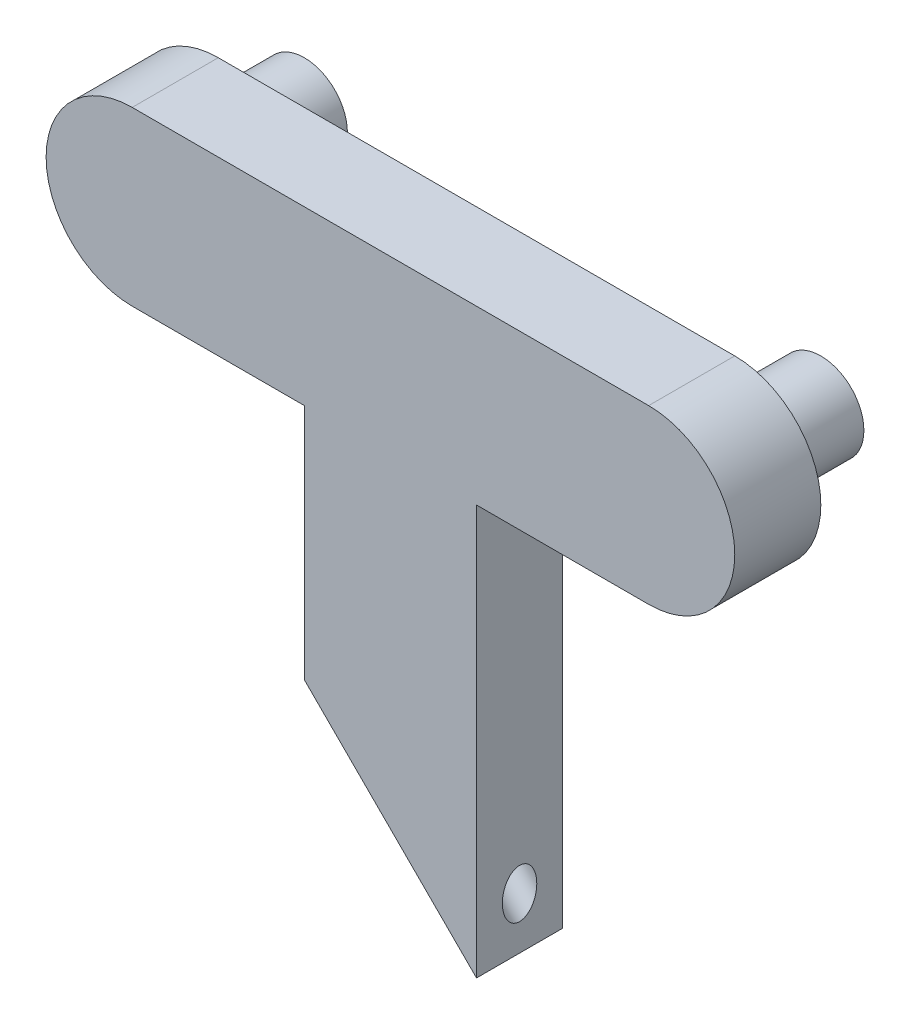
SolidWorks part; units mm, degrees
ref_plane "Piano frontale" through (0, 0, 0) normal (0, 0, 1) x (1, 0, 0)
ref_plane "Piano superiore" through (0, 0, 0) normal (0, 1, 0) x (1, 0, 0)
ref_plane "Piano destro" through (0, 0, 0) normal (1, 0, 0) x (0, 0, -1)
sketch "Schizzo1" plane through (0, 0, 0) normal (0, 0, 1) x (1, 0, 0)
  line L1 (-13.208, 5) -> (16.792, 5)
  line L2 (-13.208, -5) -> (-3.208, -5)
  line L3 (6.792, -28.7941) -> (6.792, -18.7941)
  line L4 (-3.208, -18.7941) -> (6.792, -28.7941)
  line L5 (6.792, -5) -> (16.792, -5)
  line L7 (-3.208, -5) -> (-3.208, -18.7941)
  line L9 (6.792, -5) -> (6.792, -18.7941)
  line L10 (6.792, 0) -> (16.792, 0) construction
  arc A0 (-13.208, 5) -> (-13.208, -5) centre (-13.208, 0) ccw
  arc A1 (16.792, -5) -> (16.792, 5) centre (16.792, 0) ccw
  point P3 (1.792, 0)
  dimension "D1" = 30
  dimension "D2" = 10
  dimension "D3" = 10
  dimension "D4" = 10
extrude "Estrusione-Estrusione3" add sketch "Schizzo1" along normal blind 5 contours L2 L7 L4 L3 L9 L5 A1 L1 A0
sketch "Schizzo3" plane through (0, 0, 0) normal (0, 0, -1) x (-1, 0, 0)
  line L6 (13.208, 5) -> (-16.792, 5)
  line L7 (-16.792, -5) -> (-6.792, -5)
  line L8 (-6.792, -5) -> (-6.792, -28.7941)
  line L9 (-6.792, -28.7941) -> (3.208, -18.7941)
  line L10 (3.208, -18.7941) -> (3.208, -5)
  line L11 (3.208, -5) -> (13.208, -5)
  line L12 (13.208, 5) -> (-16.792, 5) construction
  line L13 (-16.792, -5) -> (-6.792, -5) construction
  line L14 (-6.792, -5) -> (-6.792, -28.7941) construction
  line L15 (-6.792, -28.7941) -> (3.208, -18.7941) construction
  line L16 (3.208, -18.7941) -> (3.208, -5) construction
  line L17 (3.208, -5) -> (13.208, -5) construction
  circle A0 centre (-16.792, 0) radius 2.5
  circle A1 centre (13.208, 0) radius 2.5
  arc A2 (13.208, -5) -> (13.208, 5) centre (13.208, 0) ccw
  arc A3 (-16.792, 5) -> (-16.792, -5) centre (-16.792, 0) ccw
  arc A4 (13.208, -5) -> (13.208, 5) centre (13.208, 0) ccw construction
  arc A5 (-16.792, 5) -> (-16.792, -5) centre (-16.792, 0) ccw construction
  dimension "D1" = 0
extrude "Estrusione-Estrusione4" add sketch "Schizzo3" along normal blind 5
ref_plane "Piano1" through (17.7931, -17.7931, 0) normal (-0.7071, 0.7071, 0) x (0, 0, -1)
sketch "Schizzo6" plane through (17.7931, -17.7931, 0) normal (-0.7071, 0.7071, 0) x (0, 0, -1)
  line L0 (0, -1.2671) -> (0, 15.5578) construction
  circle A0 centre (-2.5, 13.4355) radius 1
  dimension "D1" = 2
  dimension "D2" = 2.5
extrude "Taglio-Estrusione1" cut sketch "Schizzo6" along normal up to surface (15.2645 mm away) up to face at (-3.208, -11.8971, 2.5)
